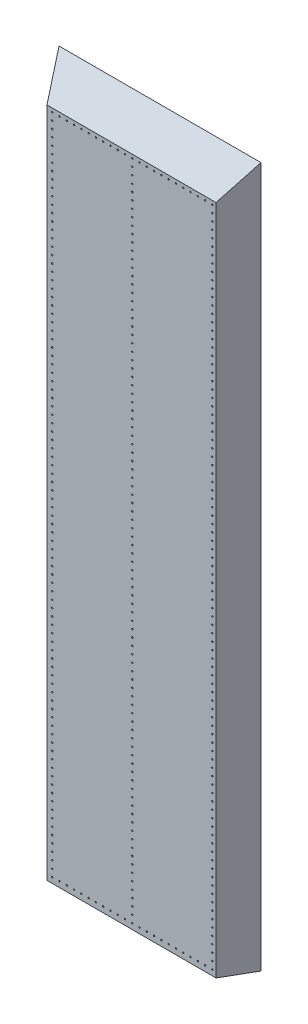
SolidWorks part; units mm, degrees
ref_plane "Front Plane" through (0, 0, 0) normal (0, 0, 1) x (1, 0, 0)
ref_plane "Top Plane" through (0, 0, 0) normal (0, 1, 0) x (1, 0, 0)
ref_plane "Right Plane" through (0, 0, 0) normal (1, 0, 0) x (0, 0, -1)
sketch "Sketch2" plane through (0, 0, 0) normal (0, 1, 0) x (1, 0, 0)
  line L0 (0, 0) -> (0, 633.6655) construction
  line L1 (-580.6, 0) -> (580.6, 0)
  line L2 (580.6, 0) -> (693.7607, 196)
  line L3 (693.7607, 196) -> (-693.7607, 196)
  line L4 (-580.6, 0) -> (-693.7607, 196)
  point P8 (0, 196)
  dimension "D1" = 580.6
  dimension "D2" = 120
  dimension "D3" = 196
extrude "Boss-Extrude1" add sketch "Sketch2" against normal blind 4809
chamfer "Chamfer1" distance 196 angle 45 1 edges at (0, 0, 0)
sketch "Sketch3" plane through (0, 0, 0) normal (0, 0, 1) x (1, 0, 0)
  circle A0 centre (-544.4, -221) radius 4.7625
  circle A1 centre (-494.4, -221) radius 4.7625
  circle A2 centre (-444.4, -221) radius 4.7625
  circle A3 centre (-394.4, -221) radius 4.7625
  circle A4 centre (-344.4, -221) radius 4.7625
  circle A5 centre (-294.4, -221) radius 4.7625
  circle A6 centre (-244.4, -221) radius 4.7625
  circle A7 centre (-194.4, -221) radius 4.7625
  circle A8 centre (-144.4, -221) radius 4.7625
  circle A9 centre (-94.4, -221) radius 4.7625
  circle A10 centre (-44.4, -221) radius 4.7625
  circle A11 centre (5.6, -221) radius 4.7625
  circle A12 centre (55.6, -221) radius 4.7625
  circle A13 centre (105.6, -221) radius 4.7625
  circle A14 centre (155.6, -221) radius 4.7625
  circle A15 centre (205.6, -221) radius 4.7625
  circle A16 centre (255.6, -221) radius 4.7625
  circle A17 centre (305.6, -221) radius 4.7625
  circle A18 centre (355.6, -221) radius 4.7625
  circle A19 centre (405.6, -221) radius 4.7625
  circle A20 centre (455.6, -221) radius 4.7625
  circle A21 centre (505.6, -221) radius 4.7625
  circle A22 centre (555.6, -221) radius 4.7625
  circle A23 centre (-494.4, -4771) radius 4.7625
  circle A24 centre (-444.4, -4771) radius 4.7625
  circle A25 centre (-394.4, -4771) radius 4.7625
  circle A26 centre (-344.4, -4771) radius 4.7625
  circle A27 centre (-294.4, -4771) radius 4.7625
  circle A28 centre (-244.4, -4771) radius 4.7625
  circle A29 centre (-194.4, -4771) radius 4.7625
  circle A30 centre (-144.4, -4771) radius 4.7625
  circle A31 centre (-94.4, -4771) radius 4.7625
  circle A32 centre (-44.4, -4771) radius 4.7625
  circle A33 centre (5.6, -4771) radius 4.7625
  circle A34 centre (55.6, -4771) radius 4.7625
  circle A35 centre (105.6, -4771) radius 4.7625
  circle A36 centre (155.6, -4771) radius 4.7625
  circle A37 centre (205.6, -4771) radius 4.7625
  circle A38 centre (255.6, -4771) radius 4.7625
  circle A39 centre (305.6, -4771) radius 4.7625
  circle A40 centre (355.6, -4771) radius 4.7625
  circle A41 centre (405.6, -4771) radius 4.7625
  circle A42 centre (455.6, -4771) radius 4.7625
  circle A43 centre (505.6, -4771) radius 4.7625
  circle A44 centre (555.6, -4771) radius 4.7625
  circle A45 centre (-544.4, -4771) radius 4.7625
  circle A46 centre (5.6, -221) radius 4.7625
  circle A47 centre (555.6, -221) radius 4.7625
  circle A48 centre (5.6, -271) radius 4.7625
  circle A49 centre (555.6, -271) radius 4.7625
  circle A50 centre (5.6, -321) radius 4.7625
  circle A51 centre (555.6, -321) radius 4.7625
  circle A52 centre (5.6, -371) radius 4.7625
  circle A53 centre (555.6, -371) radius 4.7625
  circle A54 centre (5.6, -421) radius 4.7625
  circle A55 centre (555.6, -421) radius 4.7625
  circle A56 centre (5.6, -471) radius 4.7625
  circle A57 centre (555.6, -471) radius 4.7625
  circle A58 centre (5.6, -521) radius 4.7625
  circle A59 centre (555.6, -521) radius 4.7625
  circle A60 centre (5.6, -571) radius 4.7625
  circle A61 centre (555.6, -571) radius 4.7625
  circle A62 centre (5.6, -621) radius 4.7625
  circle A63 centre (555.6, -621) radius 4.7625
  circle A64 centre (5.6, -671) radius 4.7625
  circle A65 centre (555.6, -671) radius 4.7625
  circle A66 centre (5.6, -721) radius 4.7625
  circle A67 centre (555.6, -721) radius 4.7625
  circle A68 centre (5.6, -771) radius 4.7625
  circle A69 centre (555.6, -771) radius 4.7625
  circle A70 centre (5.6, -821) radius 4.7625
  circle A71 centre (555.6, -821) radius 4.7625
  circle A72 centre (5.6, -871) radius 4.7625
  circle A73 centre (555.6, -871) radius 4.7625
  circle A74 centre (5.6, -921) radius 4.7625
  circle A75 centre (555.6, -921) radius 4.7625
  circle A76 centre (5.6, -971) radius 4.7625
  circle A77 centre (555.6, -971) radius 4.7625
  circle A78 centre (5.6, -1021) radius 4.7625
  circle A79 centre (555.6, -1021) radius 4.7625
  circle A80 centre (5.6, -1071) radius 4.7625
  circle A81 centre (555.6, -1071) radius 4.7625
  circle A82 centre (5.6, -1121) radius 4.7625
  circle A83 centre (555.6, -1121) radius 4.7625
  circle A84 centre (5.6, -1171) radius 4.7625
  circle A85 centre (555.6, -1171) radius 4.7625
  circle A86 centre (5.6, -1221) radius 4.7625
  circle A87 centre (555.6, -1221) radius 4.7625
  circle A88 centre (5.6, -1271) radius 4.7625
  circle A89 centre (555.6, -1271) radius 4.7625
  circle A90 centre (5.6, -1321) radius 4.7625
  circle A91 centre (555.6, -1321) radius 4.7625
  circle A92 centre (5.6, -1371) radius 4.7625
  circle A93 centre (555.6, -1371) radius 4.7625
  circle A94 centre (5.6, -1421) radius 4.7625
  circle A95 centre (555.6, -1421) radius 4.7625
  circle A96 centre (5.6, -1471) radius 4.7625
  circle A97 centre (555.6, -1471) radius 4.7625
  circle A98 centre (5.6, -1521) radius 4.7625
  circle A99 centre (555.6, -1521) radius 4.7625
  circle A100 centre (5.6, -1571) radius 4.7625
  circle A101 centre (555.6, -1571) radius 4.7625
  circle A102 centre (5.6, -1621) radius 4.7625
  circle A103 centre (555.6, -1621) radius 4.7625
  circle A104 centre (5.6, -1671) radius 4.7625
  circle A105 centre (555.6, -1671) radius 4.7625
  circle A106 centre (5.6, -1721) radius 4.7625
  circle A107 centre (555.6, -1721) radius 4.7625
  circle A108 centre (5.6, -1771) radius 4.7625
  circle A109 centre (555.6, -1771) radius 4.7625
  circle A110 centre (5.6, -1821) radius 4.7625
  circle A111 centre (555.6, -1821) radius 4.7625
  circle A112 centre (5.6, -1871) radius 4.7625
  circle A113 centre (555.6, -1871) radius 4.7625
  circle A114 centre (5.6, -1921) radius 4.7625
  circle A115 centre (555.6, -1921) radius 4.7625
  circle A116 centre (5.6, -1971) radius 4.7625
  circle A117 centre (555.6, -1971) radius 4.7625
  circle A118 centre (5.6, -2021) radius 4.7625
  circle A119 centre (555.6, -2021) radius 4.7625
  circle A120 centre (5.6, -2071) radius 4.7625
  circle A121 centre (555.6, -2071) radius 4.7625
  circle A122 centre (5.6, -2121) radius 4.7625
  circle A123 centre (555.6, -2121) radius 4.7625
  circle A124 centre (5.6, -2171) radius 4.7625
  circle A125 centre (555.6, -2171) radius 4.7625
  circle A126 centre (5.6, -2221) radius 4.7625
  circle A127 centre (555.6, -2221) radius 4.7625
  circle A128 centre (5.6, -2271) radius 4.7625
  circle A129 centre (555.6, -2271) radius 4.7625
  circle A130 centre (5.6, -2321) radius 4.7625
  circle A131 centre (555.6, -2321) radius 4.7625
  circle A132 centre (5.6, -2371) radius 4.7625
  circle A133 centre (555.6, -2371) radius 4.7625
  circle A134 centre (5.6, -2421) radius 4.7625
  circle A135 centre (555.6, -2421) radius 4.7625
  circle A136 centre (5.6, -2471) radius 4.7625
  circle A137 centre (555.6, -2471) radius 4.7625
  circle A138 centre (5.6, -2521) radius 4.7625
  circle A139 centre (555.6, -2521) radius 4.7625
  circle A140 centre (5.6, -2571) radius 4.7625
  circle A141 centre (555.6, -2571) radius 4.7625
  circle A142 centre (5.6, -2621) radius 4.7625
  circle A143 centre (555.6, -2621) radius 4.7625
  circle A144 centre (5.6, -2671) radius 4.7625
  circle A145 centre (555.6, -2671) radius 4.7625
  circle A146 centre (5.6, -2721) radius 4.7625
  circle A147 centre (555.6, -2721) radius 4.7625
  circle A148 centre (5.6, -2771) radius 4.7625
  circle A149 centre (555.6, -2771) radius 4.7625
  circle A150 centre (5.6, -2821) radius 4.7625
  circle A151 centre (555.6, -2821) radius 4.7625
  circle A152 centre (5.6, -2871) radius 4.7625
  circle A153 centre (555.6, -2871) radius 4.7625
  circle A154 centre (5.6, -2921) radius 4.7625
  circle A155 centre (555.6, -2921) radius 4.7625
  circle A156 centre (5.6, -2971) radius 4.7625
  circle A157 centre (555.6, -2971) radius 4.7625
  circle A158 centre (5.6, -3021) radius 4.7625
  circle A159 centre (555.6, -3021) radius 4.7625
  circle A160 centre (5.6, -3071) radius 4.7625
  circle A161 centre (555.6, -3071) radius 4.7625
  circle A162 centre (5.6, -3121) radius 4.7625
  circle A163 centre (555.6, -3121) radius 4.7625
  circle A164 centre (5.6, -3171) radius 4.7625
  circle A165 centre (555.6, -3171) radius 4.7625
  circle A166 centre (5.6, -3221) radius 4.7625
  circle A167 centre (555.6, -3221) radius 4.7625
  circle A168 centre (5.6, -3271) radius 4.7625
  circle A169 centre (555.6, -3271) radius 4.7625
  circle A170 centre (5.6, -3321) radius 4.7625
  circle A171 centre (555.6, -3321) radius 4.7625
  circle A172 centre (5.6, -3371) radius 4.7625
  circle A173 centre (555.6, -3371) radius 4.7625
  circle A174 centre (5.6, -3421) radius 4.7625
  circle A175 centre (555.6, -3421) radius 4.7625
  circle A176 centre (5.6, -3471) radius 4.7625
  circle A177 centre (555.6, -3471) radius 4.7625
  circle A178 centre (5.6, -3521) radius 4.7625
  circle A179 centre (555.6, -3521) radius 4.7625
  circle A180 centre (5.6, -3571) radius 4.7625
  circle A181 centre (555.6, -3571) radius 4.7625
  circle A182 centre (5.6, -3621) radius 4.7625
  circle A183 centre (555.6, -3621) radius 4.7625
  circle A184 centre (5.6, -3671) radius 4.7625
  circle A185 centre (555.6, -3671) radius 4.7625
  circle A186 centre (5.6, -3721) radius 4.7625
  circle A187 centre (555.6, -3721) radius 4.7625
  circle A188 centre (5.6, -3771) radius 4.7625
  circle A189 centre (555.6, -3771) radius 4.7625
  circle A190 centre (5.6, -3821) radius 4.7625
  circle A191 centre (555.6, -3821) radius 4.7625
  circle A192 centre (5.6, -3871) radius 4.7625
  circle A193 centre (555.6, -3871) radius 4.7625
  circle A194 centre (5.6, -3921) radius 4.7625
  circle A195 centre (555.6, -3921) radius 4.7625
  circle A196 centre (5.6, -3971) radius 4.7625
  circle A197 centre (555.6, -3971) radius 4.7625
  circle A198 centre (5.6, -4021) radius 4.7625
  circle A199 centre (555.6, -4021) radius 4.7625
  circle A200 centre (5.6, -4071) radius 4.7625
  circle A201 centre (555.6, -4071) radius 4.7625
  circle A202 centre (5.6, -4121) radius 4.7625
  circle A203 centre (555.6, -4121) radius 4.7625
  circle A204 centre (5.6, -4171) radius 4.7625
  circle A205 centre (555.6, -4171) radius 4.7625
  circle A206 centre (5.6, -4221) radius 4.7625
  circle A207 centre (555.6, -4221) radius 4.7625
  circle A208 centre (5.6, -4271) radius 4.7625
  circle A209 centre (555.6, -4271) radius 4.7625
  circle A210 centre (5.6, -4321) radius 4.7625
  circle A211 centre (555.6, -4321) radius 4.7625
  circle A212 centre (5.6, -4371) radius 4.7625
  circle A213 centre (555.6, -4371) radius 4.7625
  circle A214 centre (5.6, -4421) radius 4.7625
  circle A215 centre (555.6, -4421) radius 4.7625
  circle A216 centre (5.6, -4471) radius 4.7625
  circle A217 centre (555.6, -4471) radius 4.7625
  circle A218 centre (5.6, -4521) radius 4.7625
  circle A219 centre (555.6, -4521) radius 4.7625
  circle A220 centre (5.6, -4571) radius 4.7625
  circle A221 centre (555.6, -4571) radius 4.7625
  circle A222 centre (5.6, -4621) radius 4.7625
  circle A223 centre (555.6, -4621) radius 4.7625
  circle A224 centre (5.6, -4671) radius 4.7625
  circle A225 centre (555.6, -4671) radius 4.7625
  circle A226 centre (5.6, -4721) radius 4.7625
  circle A227 centre (555.6, -4721) radius 4.7625
  circle A228 centre (5.6, -4771) radius 4.7625
  circle A229 centre (555.6, -4771) radius 4.7625
  circle A230 centre (-544.4, -271) radius 4.7625
  circle A231 centre (-544.4, -321) radius 4.7625
  circle A232 centre (-544.4, -371) radius 4.7625
  circle A233 centre (-544.4, -421) radius 4.7625
  circle A234 centre (-544.4, -471) radius 4.7625
  circle A235 centre (-544.4, -521) radius 4.7625
  circle A236 centre (-544.4, -571) radius 4.7625
  circle A237 centre (-544.4, -621) radius 4.7625
  circle A238 centre (-544.4, -671) radius 4.7625
  circle A239 centre (-544.4, -721) radius 4.7625
  circle A240 centre (-544.4, -771) radius 4.7625
  circle A241 centre (-544.4, -821) radius 4.7625
  circle A242 centre (-544.4, -871) radius 4.7625
  circle A243 centre (-544.4, -921) radius 4.7625
  circle A244 centre (-544.4, -971) radius 4.7625
  circle A245 centre (-544.4, -1021) radius 4.7625
  circle A246 centre (-544.4, -1071) radius 4.7625
  circle A247 centre (-544.4, -1121) radius 4.7625
  circle A248 centre (-544.4, -1171) radius 4.7625
  circle A249 centre (-544.4, -1221) radius 4.7625
  circle A250 centre (-544.4, -1271) radius 4.7625
  circle A251 centre (-544.4, -1321) radius 4.7625
  circle A252 centre (-544.4, -1371) radius 4.7625
  circle A253 centre (-544.4, -1421) radius 4.7625
  circle A254 centre (-544.4, -1471) radius 4.7625
  circle A255 centre (-544.4, -1521) radius 4.7625
  circle A256 centre (-544.4, -1571) radius 4.7625
  circle A257 centre (-544.4, -1621) radius 4.7625
  circle A258 centre (-544.4, -1671) radius 4.7625
  circle A259 centre (-544.4, -1721) radius 4.7625
  circle A260 centre (-544.4, -1771) radius 4.7625
  circle A261 centre (-544.4, -1821) radius 4.7625
  circle A262 centre (-544.4, -1871) radius 4.7625
  circle A263 centre (-544.4, -1921) radius 4.7625
  circle A264 centre (-544.4, -1971) radius 4.7625
  circle A265 centre (-544.4, -2021) radius 4.7625
  circle A266 centre (-544.4, -2071) radius 4.7625
  circle A267 centre (-544.4, -2121) radius 4.7625
  circle A268 centre (-544.4, -2171) radius 4.7625
  circle A269 centre (-544.4, -2221) radius 4.7625
  circle A270 centre (-544.4, -2271) radius 4.7625
  circle A271 centre (-544.4, -2321) radius 4.7625
  circle A272 centre (-544.4, -2371) radius 4.7625
  circle A273 centre (-544.4, -2421) radius 4.7625
  circle A274 centre (-544.4, -2471) radius 4.7625
  circle A275 centre (-544.4, -2521) radius 4.7625
  circle A276 centre (-544.4, -2571) radius 4.7625
  circle A277 centre (-544.4, -2621) radius 4.7625
  circle A278 centre (-544.4, -2671) radius 4.7625
  circle A279 centre (-544.4, -2721) radius 4.7625
  circle A280 centre (-544.4, -2771) radius 4.7625
  circle A281 centre (-544.4, -2821) radius 4.7625
  circle A282 centre (-544.4, -2871) radius 4.7625
  circle A283 centre (-544.4, -2921) radius 4.7625
  circle A284 centre (-544.4, -2971) radius 4.7625
  circle A285 centre (-544.4, -3021) radius 4.7625
  circle A286 centre (-544.4, -3071) radius 4.7625
  circle A287 centre (-544.4, -3121) radius 4.7625
  circle A288 centre (-544.4, -3171) radius 4.7625
  circle A289 centre (-544.4, -3221) radius 4.7625
  circle A290 centre (-544.4, -3271) radius 4.7625
  circle A291 centre (-544.4, -3321) radius 4.7625
  circle A292 centre (-544.4, -3371) radius 4.7625
  circle A293 centre (-544.4, -3421) radius 4.7625
  circle A294 centre (-544.4, -3471) radius 4.7625
  circle A295 centre (-544.4, -3521) radius 4.7625
  circle A296 centre (-544.4, -3571) radius 4.7625
  circle A297 centre (-544.4, -3621) radius 4.7625
  circle A298 centre (-544.4, -3671) radius 4.7625
  circle A299 centre (-544.4, -3721) radius 4.7625
  circle A300 centre (-544.4, -3771) radius 4.7625
  circle A301 centre (-544.4, -3821) radius 4.7625
  circle A302 centre (-544.4, -3871) radius 4.7625
  circle A303 centre (-544.4, -3921) radius 4.7625
  circle A304 centre (-544.4, -3971) radius 4.7625
  circle A305 centre (-544.4, -4021) radius 4.7625
  circle A306 centre (-544.4, -4071) radius 4.7625
  circle A307 centre (-544.4, -4121) radius 4.7625
  circle A308 centre (-544.4, -4171) radius 4.7625
  circle A309 centre (-544.4, -4221) radius 4.7625
  circle A310 centre (-544.4, -4271) radius 4.7625
  circle A311 centre (-544.4, -4321) radius 4.7625
  circle A312 centre (-544.4, -4371) radius 4.7625
  circle A313 centre (-544.4, -4421) radius 4.7625
  circle A314 centre (-544.4, -4471) radius 4.7625
  circle A315 centre (-544.4, -4521) radius 4.7625
  circle A316 centre (-544.4, -4571) radius 4.7625
  circle A317 centre (-544.4, -4621) radius 4.7625
  circle A318 centre (-544.4, -4671) radius 4.7625
  circle A319 centre (-544.4, -4721) radius 4.7625
  circle A320 centre (-544.4, -4771) radius 4.7625
  dimension "D1" = 23
  dimension "D2" = 2
  dimension "D3" = 3
  dimension "D4" = 92
extrude "Cut-Extrude1" cut sketch "Sketch3" against normal through all
